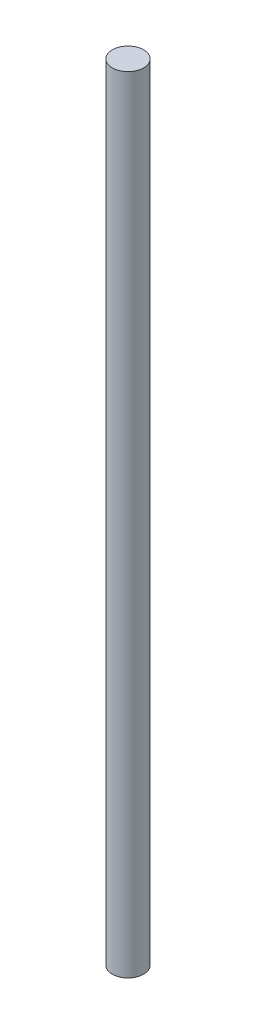
SolidWorks part; units mm, degrees
ref_plane "Front Plane" through (0, 0, 0) normal (0, 0, 1) x (1, 0, 0)
ref_plane "Top Plane" through (0, 0, 0) normal (0, 1, 0) x (1, 0, 0)
ref_plane "Right Plane" through (0, 0, 0) normal (1, 0, 0) x (0, 0, -1)
sketch "Sketch1" plane through (0, 0, 0) normal (0, 1, 0) x (1, 0, 0)
  circle A0 centre (0, 0) radius 6
extrude "Boss-Extrude1" add sketch "Sketch1" along normal blind 300
ref_axis "Midline" through (0, 300, 0) along (0, -1, 0)
